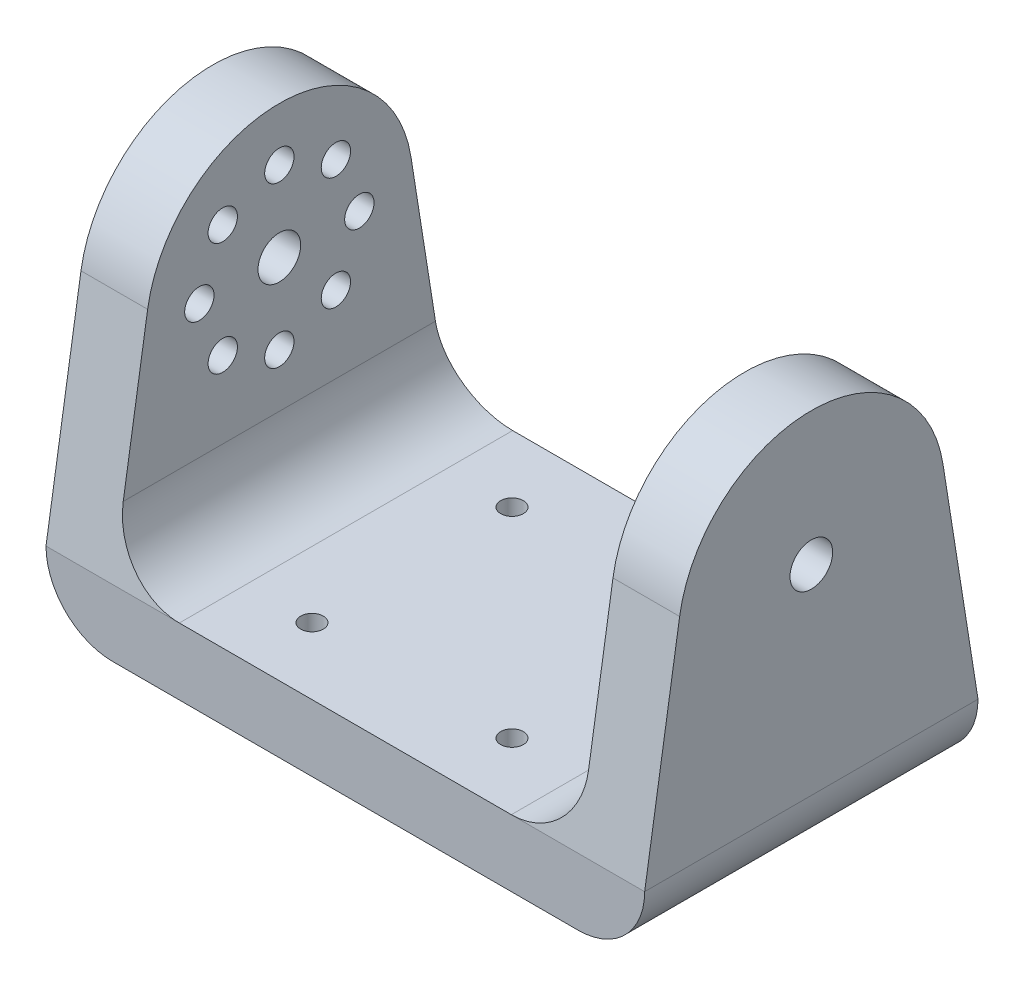
SolidWorks part; units mm, degrees
material "ABS"
ref_plane "正面" through (0, 0, 0) normal (0, 0, 1) x (1, 0, 0)
ref_plane "平面" through (0, 0, 0) normal (0, 1, 0) x (1, 0, 0)
ref_plane "右側面" through (0, 0, 0) normal (1, 0, 0) x (0, 0, -1)
sketch "ｽｹｯﾁ1" plane through (0, 0, 0) normal (0, 1, 0) x (1, 0, 0)
  line L1 (22.45, 0) -> (-22.45, 0)
  line L2 (22.45, 0) -> (22.45, 25)
  line L3 (22.45, 25) -> (-22.45, 25)
  line L4 (-22.45, 0) -> (-22.45, 25)
  dimension "D1" = 44.9
  dimension "D2" = 25
extrude "ﾎﾞｽ - 押し出し1" add sketch "ｽｹｯﾁ1" along normal blind 5
sketch "ｽｹｯﾁ2" plane through (-22.45, 0, 0) normal (-1, 0, 0) x (0, 0, 1)
  line L0 (-25, 5) -> (0, 5)
  line L1 (0, 5) -> (-2.6231, 21.5641)
  line L2 (-22.3769, 21.5641) -> (-25, 5)
  line L3 (-12.5, 5) -> (-12.5, 20) construction
  arc A0 (-2.6231, 21.5641) -> (-22.3769, 21.5641) centre (-12.5, 20) ccw
  circle A1 centre (-12.5, 20) radius 6 construction
  circle A2 centre (-12.5, 26) radius 1.1
  circle A3 centre (-8.2574, 24.2426) radius 1.1
  circle A4 centre (-6.5, 20) radius 1.1
  circle A5 centre (-8.2574, 15.7574) radius 1.1
  circle A6 centre (-12.5, 14) radius 1.1
  circle A7 centre (-16.7426, 15.7574) radius 1.1
  circle A8 centre (-18.5, 20) radius 1.1
  circle A9 centre (-16.7426, 24.2426) radius 1.1
  circle A10 centre (-12.5, 20) radius 1.6
  point P28 (-12.5, 20)
  dimension "D1" = 20
  dimension "D3" = 12
  dimension "D4" = 2.2
  dimension "D6" = 3.2
  dimension "D2" = 15
  dimension "D5" = 8
extrude "ﾎﾞｽ - 押し出し2" add sketch "ｽｹｯﾁ2" against normal blind 5
sketch "ｽｹｯﾁ3" plane through (22.45, 0, 0) normal (1, 0, 0) x (0, 0, -1)
  line L0 (0, 5) -> (2.6231, 21.5641) construction
  line L1 (22.3769, 21.5641) -> (25, 5) construction
  line L2 (25, 5) -> (0, 5) construction
  line L3 (0, 5) -> (2.6231, 21.5641)
  line L4 (22.3769, 21.5641) -> (25, 5)
  line L5 (25, 5) -> (0, 5)
  arc A0 (22.3769, 21.5641) -> (2.6231, 21.5641) centre (12.5, 20) ccw construction
  arc A1 (22.3769, 21.5641) -> (2.6231, 21.5641) centre (12.5, 20) ccw
  circle A2 centre (12.5, 20) radius 1.6
  dimension "D1" = 3.2
extrude "ﾎﾞｽ - 押し出し3" add sketch "ｽｹｯﾁ3" against normal blind 5
fillet "ﾌｨﾚｯﾄ1" radius 5 4 edges at (17.45, 5, -12.5) (-17.45, 5, -12.5) (22.45, 0, -12.5) (-22.45, 0, -12.5)
sketch "ｽｹｯﾁ4" plane through (0, 5, 0) normal (0, 1, 0) x (1, 0, 0)
  line L0 (0, 25) -> (0, 0) construction
  line L1 (12.45, 25) -> (-12.45, 25) construction
  line L2 (-12.45, 0) -> (12.45, 0) construction
  line L3 (-12.45, 12.5) -> (12.45, 12.5) construction
  line L4 (-12.45, 25) -> (-12.45, 0) construction
  line L5 (12.45, 0) -> (12.45, 25) construction
  line L7 (-7.5, 20) -> (7.5, 20) construction
  line L8 (-7.5, 20) -> (-7.5, 5) construction
  line L9 (-7.5, 5) -> (7.5, 5) construction
  line L10 (7.5, 20) -> (7.5, 5) construction
  line L11 (-7.5, 20) -> (7.5, 5) construction
  line L12 (-7.5, 5) -> (7.5, 20) construction
  circle A0 centre (-7.5, 20) radius 0.85
  circle A1 centre (7.5, 20) radius 0.85
  circle A2 centre (7.5, 5) radius 0.85
  circle A3 centre (-7.5, 5) radius 0.85
  point P12 (0, 12.5)
  dimension "D3" = 1.7
  dimension "D1" = 15
  dimension "D2" = 15
extrude "ｶｯﾄ - 押し出し1" cut sketch "ｽｹｯﾁ4" against normal blind 5
